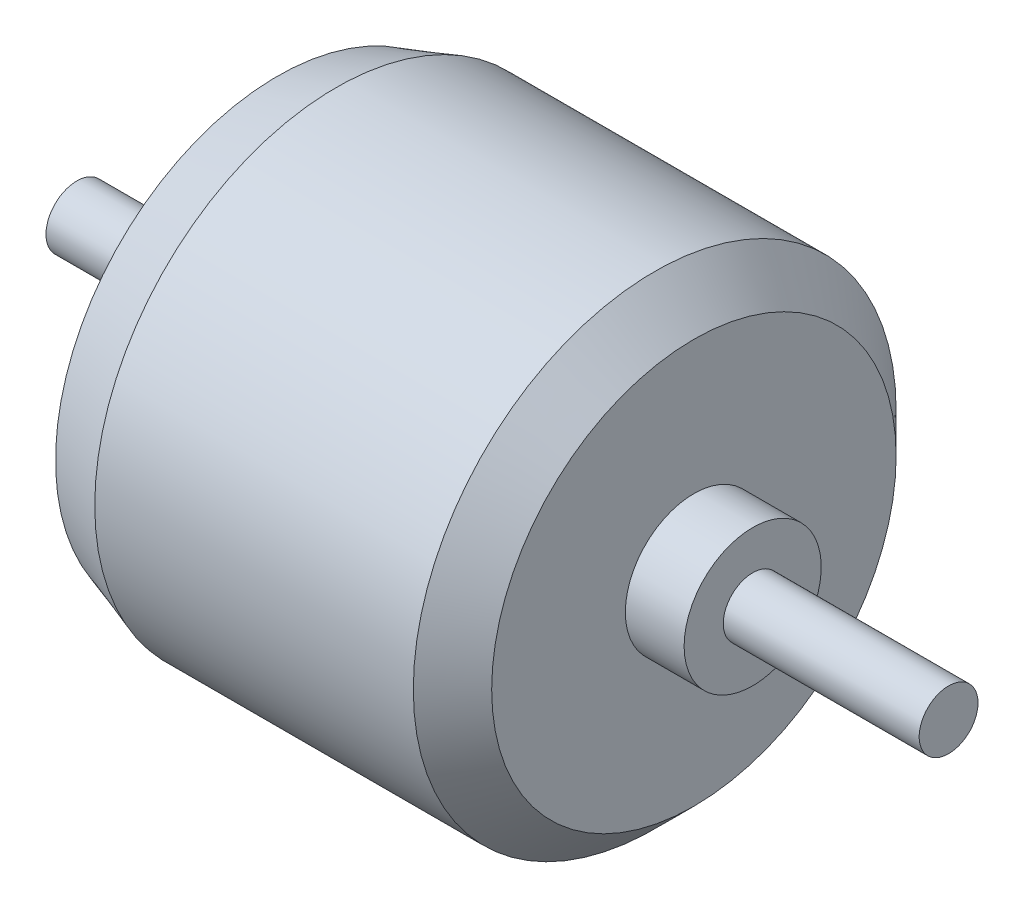
SolidWorks part; units mm, degrees
ref_plane "Front Plane" through (0, 0, 0) normal (0, 0, 1) x (1, 0, 0)
ref_plane "Top Plane" through (0, 0, 0) normal (0, 1, 0) x (1, 0, 0)
ref_plane "Right Plane" through (0, 0, 0) normal (1, 0, 0) x (0, 0, -1)
sketch "Sketch2" plane through (0, 0, 0) normal (1, 0, 0) x (0, 0, -1)
  circle A0 centre (0, 0) radius 4
  dimension "D1" = 8
extrude "Boss-Extrude1" add sketch "Sketch2" along normal blind 26
sketch "Sketch3" plane through (26, 0, 0) normal (1, 0, 0) x (0, 0, -1)
  circle A0 centre (0, 0) radius 31.3
  dimension "D1" = 62.6
extrude "Boss-Extrude2" add sketch "Sketch3" along normal blind 54
sketch "Sketch4" plane through (26, 0, 0) normal (-1, 0, 0) x (0, 0, 1)
  line L0 (0, 22) -> (0, -22)
  line L1 (-15, 0) -> (15, 0)
  circle A0 centre (0, 22) radius 2
  circle A1 centre (0, -22) radius 2
  circle A2 centre (-15, 0) radius 2
  circle A3 centre (15, 0) radius 2
  circle A4 centre (22, 0) radius 2
  circle A5 centre (0, -22) radius 2
  circle A6 centre (-22, 0) radius 2
  circle A7 centre (0, 15) radius 2
  circle A8 centre (15, 0) radius 2
  circle A9 centre (0, -15) radius 2
  point P5 (0, 0)
  point P9 (0, 0)
  point P22 (0, 0)
  point P29 (0, 0)
  dimension "D3" = 4
  dimension "D4" = 4
  dimension "D5" = 4
  dimension "D6" = 4
  dimension "D1" = 44
  dimension "D2" = 30
  dimension "D7" = 4
  dimension "D8" = 4
extrude "Cut-Extrude1" cut sketch "Sketch4" against normal blind 8 contours A0 | A3 | A1 | A6 | L0 A7 | L0 A7 | L0 A9 | L0 A9 | A4 | A2 region at (26, 1.9434, 15) region at (26, -20.6258, 1.3742) region at (26, -15, 0.8488) region at (26, -15, -0.8488) region at (26, 15, 0.8488) region at (26, 15, -0.8488) region at (26, 23.3742, -1.3742) region at (26, 0, 22) region at (26, 0, -22)
chamfer "Chamfer1" distance 2.54 distance2 7.62 1 edges at (26, 0, -31.3) first distance on face at (26, 22, 2)
chamfer "Chamfer2" distance 5.08 1 edges at (80, 0, -31.3)
sketch "Sketch5" plane through (80, 0, 0) normal (1, 0, 0) x (0, 0, -1)
  circle A0 centre (0, 0) radius 8.89
  dimension "D1" = 17.78
extrude "Boss-Extrude3" add sketch "Sketch5" along normal blind 7.62
sketch "Sketch6" plane through (87.62, 0, 0) normal (1, 0, 0) x (0, 0, -1)
  circle A0 centre (0, 0) radius 3.8128
extrude "Boss-Extrude4" add sketch "Sketch6" along normal blind 25.4
